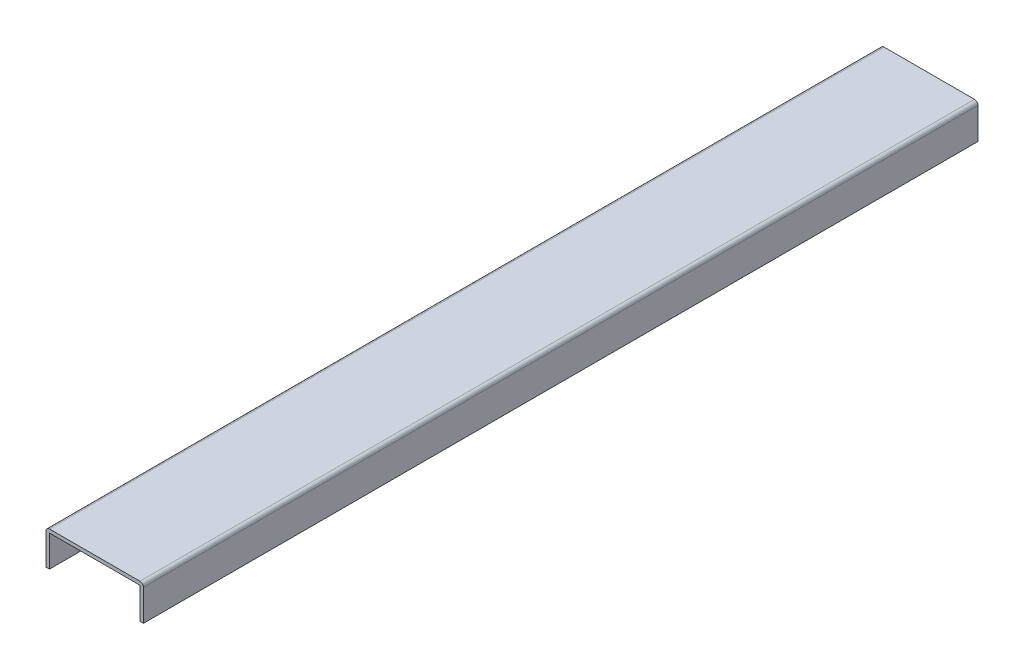
SolidWorks part; units mm, degrees
ref_plane "Plano frontal" through (0, 0, 0) normal (0, 0, 1) x (1, 0, 0)
ref_plane "Plano superior" through (0, 0, 0) normal (0, 1, 0) x (1, 0, 0)
ref_plane "Plano direito" through (0, 0, 0) normal (1, 0, 0) x (0, 0, -1)
sketch "Esboço1" plane through (0, 0, 0) normal (0, 0, 1) x (1, 0, 0)
  line L1 (-70, -25) -> (70, -25)
  line L2 (-70, -25) -> (-70, 25)
  line L3 (-70, 25) -> (70, 25)
  line L4 (70, -25) -> (70, 25)
  line L5 (-70, -25) -> (70, 25) construction
  line L6 (-70, 25) -> (70, -25) construction
  point P0 (0, 0)
  dimension "D1" = 50
  dimension "D2" = 140
extrude "Ressalto-extrusão1" add sketch "Esboço1" along normal blind 1200
fillet "Filete1" radius 5 2 edges at (70, 25, 600) (-70, 25, 600)
shell "Casca1" thickness 5 removed face at (0, 7.0118, 0) removed face at (0, -25, 600) removed face at (0, 7.0118, 1200)
